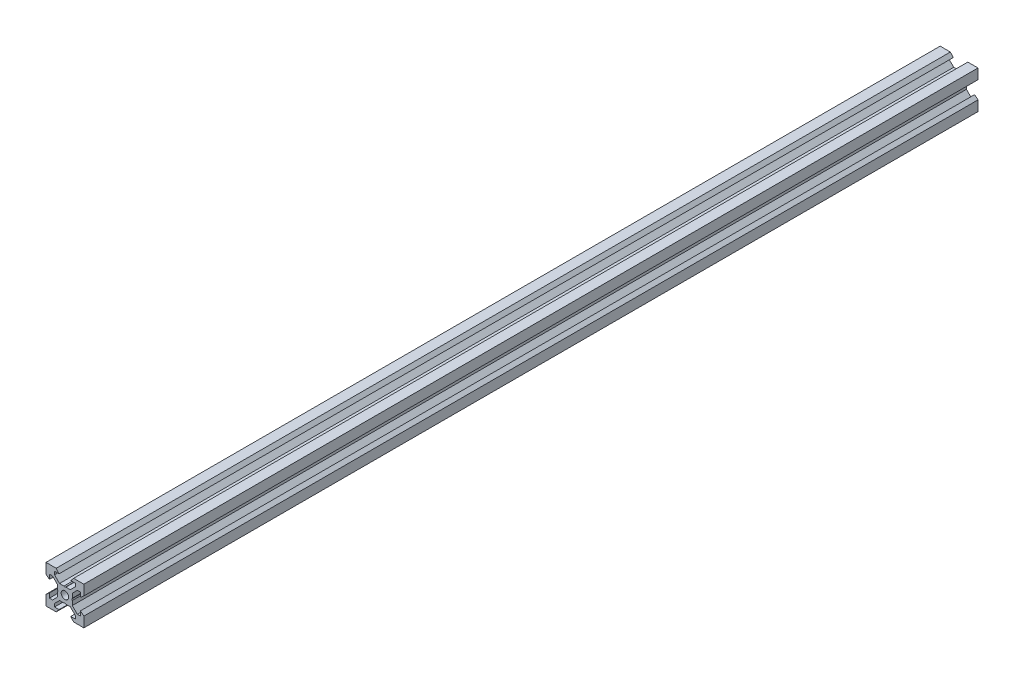
SolidWorks part; units mm, degrees
ref_plane "Front Plane" through (0, 0, 0) normal (0, 0, 1) x (1, 0, 0)
ref_plane "Top Plane" through (0, 0, 0) normal (0, 1, 0) x (1, 0, 0)
ref_plane "Right Plane" through (0, 0, 0) normal (1, 0, 0) x (0, 0, -1)
sketch "Sketch1" plane through (0, 0, 0) normal (0, 0, 1) x (1, 0, 0)
  line L0 (10, 10) -> (4.6104, 10) construction
  line L1 (10, 10) -> (10, 4.6104) construction
  line L2 (10, -10) -> (10, -4.6104) construction
  line L3 (10, -10) -> (4.6104, -10) construction
  line L4 (10, 10) -> (10, 4.6104)
  line L5 (6.5607, 5.5) -> (8.2, 5.5)
  line L6 (5.5, 8.2) -> (5.5, 6.5607)
  line L7 (10, 10) -> (4.6104, 10)
  line L8 (10, 10) -> (10, 4.6104)
  line L9 (6.5607, 5.5) -> (3.9, 2.8393)
  line L10 (5.5, 6.5607) -> (2.8393, 3.9)
  line L11 (10, 4.6104) -> (8.2, 3.1)
  line L12 (4.6104, 10) -> (3.1, 8.2)
  line L13 (8.2, 3.1) -> (8.2, 5.5)
  line L14 (3.1, 8.2) -> (5.5, 8.2)
  line L15 (-6.5607, 5.5) -> (-8.2, 5.5)
  line L16 (6.5607, -5.5) -> (8.2, -5.5)
  line L17 (3.1, -8.2) -> (5.5, -8.2)
  line L18 (8.2, -3.1) -> (8.2, -5.5)
  line L19 (4.6104, -10) -> (3.1, -8.2)
  line L20 (10, -4.6104) -> (8.2, -3.1)
  line L21 (0.5196, -3.9) -> (0, -3.6)
  line L22 (0.5196, 3.9) -> (0, 3.6)
  line L23 (3.6, 0) -> (3.9, -0.5196)
  line L24 (3.9, 0.5196) -> (3.6, 0)
  line L25 (3.9, 0.5196) -> (3.9, 2.8393)
  line L26 (2.8393, 3.9) -> (0.5196, 3.9)
  line L27 (3.9, -2.8393) -> (3.9, -0.5196)
  line L28 (2.8393, -3.9) -> (0.5196, -3.9)
  line L29 (5.5, -6.5607) -> (2.8393, -3.9)
  line L30 (6.5607, -5.5) -> (3.9, -2.8393)
  line L31 (10, -10) -> (10, -4.6104)
  line L32 (10, -10) -> (4.6104, -10)
  line L33 (5.5, -8.2) -> (5.5, -6.5607)
  line L34 (-6.5607, -5.5) -> (-8.2, -5.5)
  line L35 (10, -10) -> (10, -4.6104)
  line L36 (0, 0) -> (0, 8.2) construction
  line L37 (-10, -10) -> (-4.6104, -10) construction
  line L38 (-10, -10) -> (-10, -4.6104) construction
  line L39 (-10, 10) -> (-10, 4.6104) construction
  line L40 (-10, 10) -> (-4.6104, 10) construction
  line L41 (-10, -10) -> (-10, -4.6104)
  line L43 (-5.5, -8.2) -> (-5.5, -6.5607)
  line L44 (-10, -10) -> (-4.6104, -10)
  line L45 (-10, -10) -> (-10, -4.6104)
  line L46 (-6.5607, -5.5) -> (-3.9, -2.8393)
  line L47 (-5.5, -6.5607) -> (-2.8393, -3.9)
  line L48 (-2.8393, -3.9) -> (-0.5196, -3.9)
  line L49 (-3.9, -2.8393) -> (-3.9, -0.5196)
  line L50 (-2.8393, 3.9) -> (-0.5196, 3.9)
  line L51 (-3.9, 0.5196) -> (-3.9, 2.8393)
  line L52 (-3.9, 0.5196) -> (-3.6, 0)
  line L53 (-3.6, 0) -> (-3.9, -0.5196)
  line L54 (-0.5196, 3.9) -> (0, 3.6)
  line L55 (-0.5196, -3.9) -> (0, -3.6)
  line L56 (-10, -4.6104) -> (-8.2, -3.1)
  line L57 (-4.6104, -10) -> (-3.1, -8.2)
  line L58 (-8.2, -3.1) -> (-8.2, -5.5)
  line L59 (-3.1, -8.2) -> (-5.5, -8.2)
  line L60 (-10, -10) -> (10, -10) construction
  line L61 (-10, -10) -> (-10, 10) construction
  line L62 (-3.1, 8.2) -> (-5.5, 8.2)
  line L63 (-8.2, 3.1) -> (-8.2, 5.5)
  line L64 (-4.6104, 10) -> (-3.1, 8.2)
  line L65 (-10, 4.6104) -> (-8.2, 3.1)
  line L66 (-5.5, 6.5607) -> (-2.8393, 3.9)
  line L67 (-6.5607, 5.5) -> (-3.9, 2.8393)
  line L68 (-10, 10) -> (-10, 4.6104)
  line L69 (-10, 10) -> (-4.6104, 10)
  line L70 (-5.5, 8.2) -> (-5.5, 6.5607)
  line L71 (-10, 10) -> (10, 10) construction
  line L72 (-10, 10) -> (-10, 4.6104)
  line L73 (10, -10) -> (10, 10) construction
  line L74 (-10, -10) -> (10, 10) construction
  line L75 (-10, 10) -> (10, -10) construction
  circle A0 centre (0, 0) radius 2
  dimension "D7" = 4
  dimension "D1" = 20
  dimension "D2" = 5.3896
  dimension "D3" = 4.5
  dimension "D4" = 50
  dimension "D5" = 1.8
  dimension "D6" = 1.5104
  dimension "D8" = 5.5
  dimension "D9" = 120
  dimension "D10" = 0.3
  dimension "D11" = 2.3197
  dimension "D12" = 7.8
  dimension "D13" = 7.8
  dimension "D14" = 1.5
  dimension "D15" = 2.6607
extrude "Boss-Extrude1" add sketch "Sketch1" along normal mid plane 472.69 contours L70 L62 L64 L69 L68 L65 L63 L15 L67 L51 L52 L53 L49 L46 L34 L58 L56 L41 L44 L57 L59 L43 L47 L48 L55 L21 L28 L29 L33 L17 L19 L32 L31 L20 L18 L16 L30 L27 L23 L24 L25 L9 L5 L13 L11 L4 L7 L12 L14 L6 L10 region at (9.7172, 7.3052, 0)
